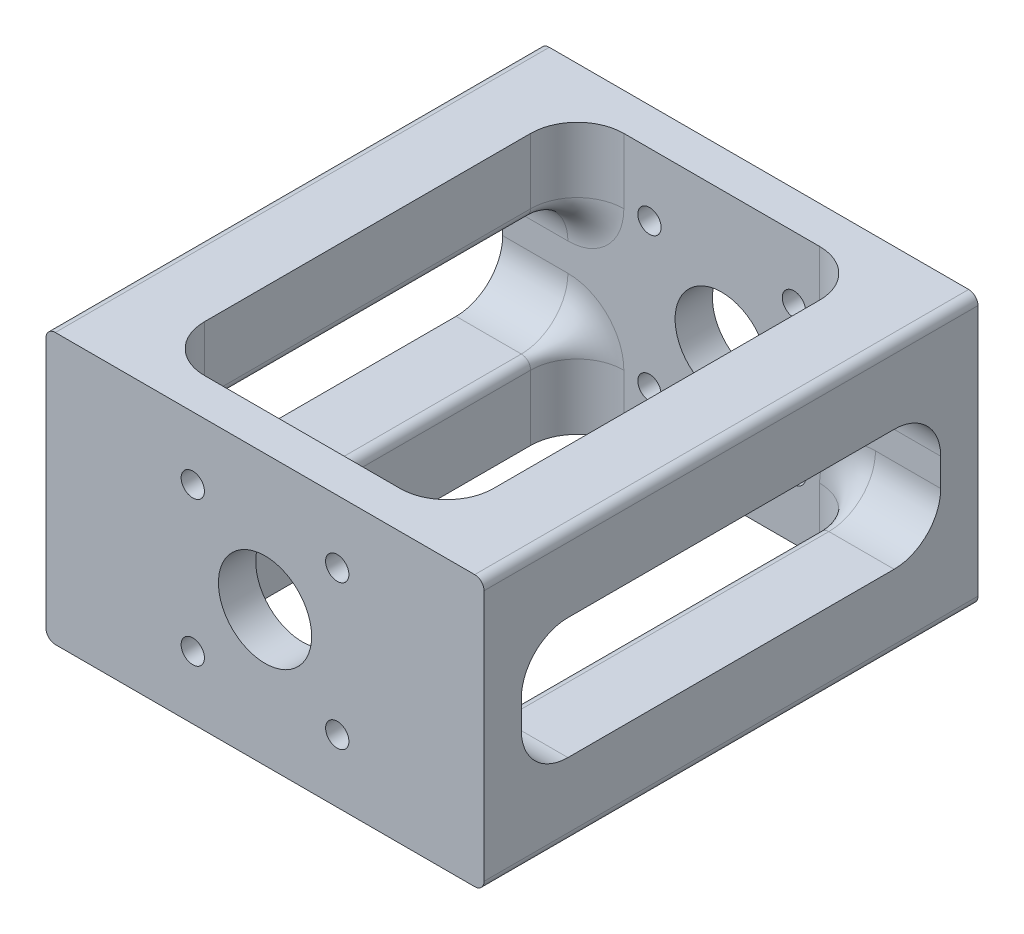
SolidWorks part; units mm, degrees
ref_plane "Front Plane" through (0, 0, 0) normal (0, 0, 1) x (1, 0, 0)
ref_plane "Top Plane" through (0, 0, 0) normal (0, 1, 0) x (1, 0, 0)
ref_plane "Right Plane" through (0, 0, 0) normal (1, 0, 0) x (0, 0, -1)
sketch "Sketch1" plane through (0, 0, 0) normal (0, 0, 1) x (1, 0, 0)
  line L8 (-23.5, -14.5) -> (-23.5, 14.5)
  line L9 (-23.5, -14.5) -> (23.5, -14.5)
  line L10 (-23.5, 14.5) -> (23.5, 14.5)
  line L11 (23.5, -14.5) -> (23.5, 14.5)
  line L12 (0, 0) -> (-30.3506, 0) construction
  line L13 (0, 0) -> (0, -30.5673) construction
  circle A0 centre (7.75, -7.75) radius 1.25
  circle A1 centre (7.75, 7.75) radius 1.25
  circle A2 centre (-7.75, 7.75) radius 1.25
  circle A4 centre (0, 0) radius 5
  circle A10 centre (-7.75, -7.75) radius 1.25
  dimension "D5" = 2.5
  dimension "D6" = 10
  dimension "D7" = 7.75
  dimension "D1" = 29
  dimension "D2" = 47
  dimension "D3" = 23.5
  dimension "D4" = 14.5
  dimension "D8" = 7.75
  dimension "D11" = 7.75
  dimension "D12" = 7.75
  dimension "D9" = 2
  dimension "D10" = 2
extrude "Boss-Extrude1" add sketch "Sketch1" against normal blind 4
sketch "Sketch3" plane through (0, 0, -4) normal (0, 0, -1) x (-1, 0, 0)
  line L0 (23.5, -14.5) -> (-23.5, -14.5) construction
  line L1 (23.5, -14.5) -> (15.5, -14.5)
  line L2 (23.5, -14.5) -> (23.5, -6.5)
  line L3 (23.5, -6.5) -> (15.5, -6.5)
  line L4 (15.5, -14.5) -> (15.5, -6.5)
  line L5 (23.5, 14.5) -> (23.5, -14.5) construction
  line L6 (0, 20.0063) -> (0, -20.0063) construction
  line L7 (30.7092, 0) -> (-30.7092, 0) construction
  line L8 (-23.5, -6.5) -> (-15.5, -6.5)
  line L9 (-15.5, -14.5) -> (-15.5, -6.5)
  line L10 (-23.5, -14.5) -> (-15.5, -14.5)
  line L11 (-23.5, -14.5) -> (-23.5, -6.5)
  line L12 (-23.5, 14.5) -> (-23.5, 6.5)
  line L13 (-23.5, 14.5) -> (-15.5, 14.5)
  line L14 (-15.5, 14.5) -> (-15.5, 6.5)
  line L15 (-23.5, 6.5) -> (-15.5, 6.5)
  line L16 (23.5, 6.5) -> (15.5, 6.5)
  line L17 (15.5, 14.5) -> (15.5, 6.5)
  line L18 (23.5, 14.5) -> (15.5, 14.5)
  line L19 (23.5, 14.5) -> (23.5, 6.5)
  point P11 (0, 0)
  point P14 (0, 0)
  dimension "D1" = 8
extrude "Boss-Extrude2" add sketch "Sketch3" along normal blind 22.5
fillet "Fillet1" radius 1 8 edges at (15.5, 6.5, -15.25) (-15.5, 6.5, -15.25) (-15.5, -6.5, -15.25) (15.5, -6.5, -15.25) (23.5, -14.5, -13.25) (23.5, 14.5, -13.25) (-23.5, 14.5, -13.25) (-23.5, -14.5, -13.25)
fillet "Fillet2" radius 5 12 edges at (15.5, -11, -4) (15.7929, -6.7929, -4) (-15.5, -11, -4) (-15.7929, -6.7929, -4) (-15.5, 11, -4) (-15.7929, 6.7929, -4) (15.5, 11, -4) (15.7929, 6.7929, -4) (20, -6.5, -4) (-20, -6.5, -4) (-20, 6.5, -4) (20, 6.5, -4)
ref_plane "Plane1" through (0, 0, -26.5) normal (0, 0, -1) x (-1, 0, 0)
mirror "Mirror3" about plane through (0, 0, -26.5) normal (0, 0, 1) of "Boss-Extrude1", "Boss-Extrude2", "Fillet1", "Fillet2"
